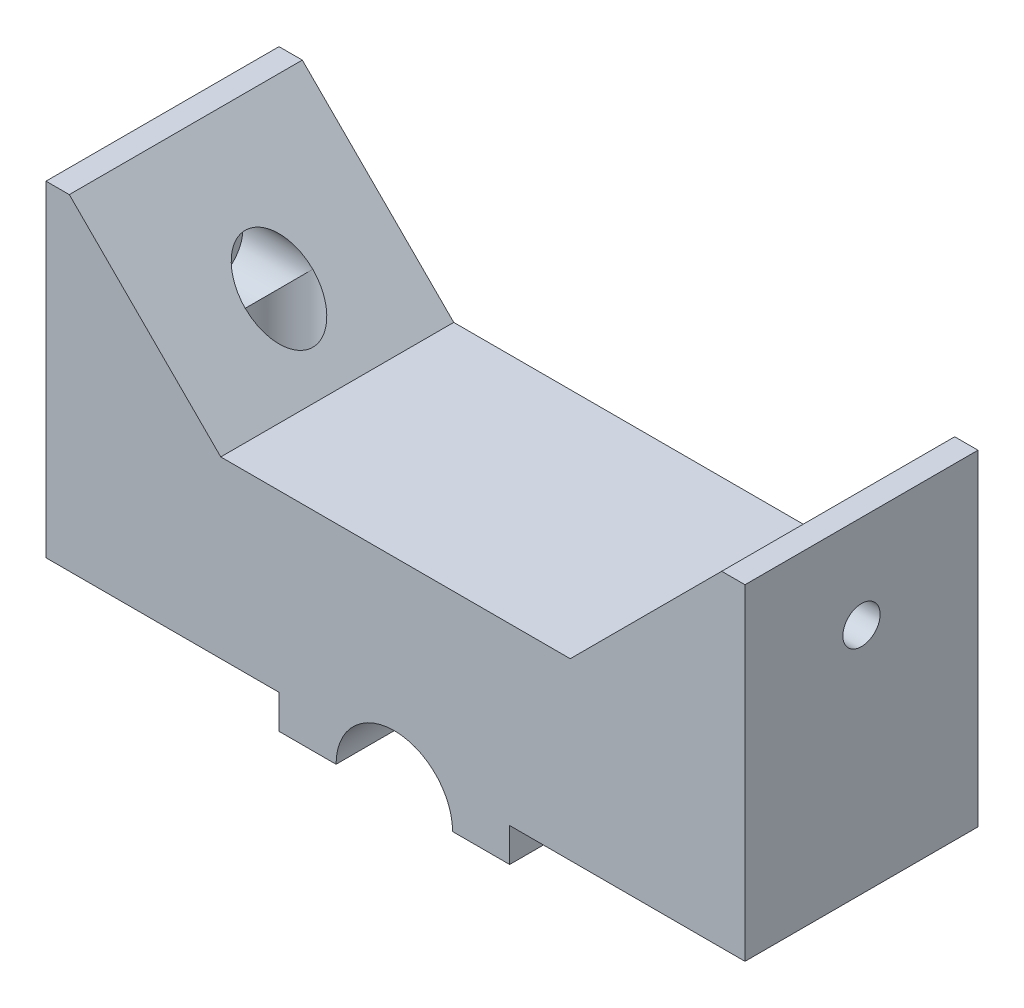
SolidWorks part; units mm, degrees
ref_plane "Plan de face" through (0, 0, 0) normal (0, 0, 1) x (1, 0, 0)
ref_plane "Plan de dessus" through (0, 0, 0) normal (0, 1, 0) x (1, 0, 0)
ref_plane "Plan de droite" through (0, 0, 0) normal (1, 0, 0) x (0, 0, -1)
sketch "Esquisse1" plane through (0, 0, 0) normal (0, 0, 1) x (1, 0, 0)
  line L0 (0, 30) -> (15, 15)
  line L1 (0, 0) -> (60, 0)
  line L2 (0, 0) -> (0, 15)
  line L3 (0, 15) -> (60, 15)
  line L4 (60, 0) -> (60, 15)
  line L5 (20, 0) -> (39.8, 0)
  line L6 (20, 0) -> (20, -2.9)
  line L7 (20, -2.9) -> (39.8, -2.9)
  line L8 (39.8, 0) -> (39.8, -2.9)
  line L9 (0, 15) -> (15, 15)
  line L10 (0, 15) -> (0, 30)
  line L11 (0, 30) -> (15, 30)
  line L12 (15, 15) -> (15, 30)
  line L13 (60, 15) -> (45, 15)
  line L14 (60, 15) -> (60, 30)
  line L15 (60, 30) -> (45, 30)
  line L16 (45, 15) -> (45, 30)
  line L17 (45, 15) -> (60, 30)
  line L19 (0, 30) -> (2, 30)
  line L20 (0, 30) -> (0, 28)
  line L21 (0, 28) -> (2, 28)
  line L22 (2, 30) -> (2, 28)
  line L23 (60, 30) -> (58, 30)
  line L24 (60, 30) -> (60, 28)
  line L25 (60, 28) -> (58, 28)
  line L26 (58, 30) -> (58, 28)
  dimension "D1" = 15
  dimension "D2" = 60
  dimension "D3" = 2.9
  dimension "D4" = 20
  dimension "D5" = 19.8
  dimension "D6" = 15
  dimension "D7" = 15
  dimension "D8" = 15
  dimension "D9" = 15
  dimension "D10" = 2
  dimension "D11" = 2
extrude "Boss.-Extru.1" add sketch "Esquisse1" along normal blind 5 contours L10 L3 L0 | L1 L4 L3 L2 | L17 L3 L14 | L8 L1 L6 L7 region at (5.0784, 19.8431, 0) region at (30, 7.5, 0) region at (54.9216, 19.8431, 0) region at (29.9, -1.45, 0)
sketch "Esquisse2" plane through (0, 0, 5) normal (0, 0, 1) x (1, 0, 0)
  line L10 (0, 28) -> (0, 0)
  line L11 (0, 0) -> (20, 0)
  line L12 (20, 0) -> (20, -2.9)
  line L13 (20, -2.9) -> (39.8, -2.9)
  line L14 (39.8, -2.9) -> (39.8, 0)
  line L15 (39.8, 0) -> (60, 0)
  line L16 (60, 0) -> (60, 28)
  line L17 (58, 28) -> (45, 15)
  line L18 (45, 15) -> (15, 15)
  line L19 (15, 15) -> (2, 28)
  line L20 (0, 28) -> (0, 0)
  line L21 (0, 0) -> (20, 0)
  line L22 (20, 0) -> (20, -2.9)
  line L23 (20, -2.9) -> (39.8, -2.9)
  line L24 (39.8, -2.9) -> (39.8, 0)
  line L25 (39.8, 0) -> (60, 0)
  line L26 (60, 0) -> (60, 28)
  line L27 (58, 28) -> (45, 15)
  line L28 (45, 15) -> (15, 15)
  line L29 (15, 15) -> (2, 28)
  line L32 (2, 28) -> (0, 28)
  line L33 (2, 28) -> (0, 28)
  line L34 (60, 28) -> (58, 28)
  line L35 (60, 28) -> (58, 28)
  circle A0 centre (29.9, -2.9) radius 5
  line M11 (0, 28) -> (0, 0)
  line M12 (0, 0) -> (20, 0)
  line M13 (20, 0) -> (20, -2.9)
  line M14 (20, -2.9) -> (39.8, -2.9)
  line M15 (39.8, -2.9) -> (39.8, 0)
  line M16 (39.8, 0) -> (60, 0)
  line M17 (60, 0) -> (60, 28)
  line M18 (58, 28) -> (45, 15)
  line M19 (45, 15) -> (15, 15)
  line M20 (15, 15) -> (2, 28)
  dimension "D2" = 10
  dimension "D1" = 0
extrude "Boss.-Extru.2" add sketch "Esquisse2" along normal blind 15 contours A0 M14 M15 M16 M17 M18 M19 M20 M11 M12 M13 region at (29.9984, 9.7289, 5)
sketch "Esquisse3" plane through (60, 0, 0) normal (1, 0, 0) x (0, 0, -1)
  line L0 (-20, 0) -> (-20, 28) construction
  line L5 (-20, 28) -> (0, 28) construction
  circle A0 centre (-10, 20) radius 1.6
  dimension "D3" = 3.2
  dimension "D1" = 10
  dimension "D2" = 8
extrude "Enlèv. mat.-Extru.1" cut sketch "Esquisse3" against normal through all contours A0 | A0 region at (60, 20, 10)
ref_plane "Plan1" through (30, 0, 0) normal (-1, 0, 0) x (0, 0, 1)
sketch "Esquisse4" plane through (30, 0, 0) normal (-1, 0, 0) x (0, 0, 1)
  circle A0 centre (10, 20) radius 1.6 construction
  circle A1 centre (10, 20) radius 1.6
  circle A2 centre (10, 20) radius 2.9
  dimension "D1" = 5.8
extrude "Enlèv. mat.-Extru.2" cut sketch "Esquisse4" against normal blind 26 and the other way blind 26
sketch "Esquisse5" plane through (0, 0, 0) normal (0, -1, 0) x (1, 0, 0)
  line L0 (39.8, 0) -> (60, 0) construction
  line L1 (60, 0) -> (60, 20) construction
  line L2 (60, 20) -> (39.8, 20) construction
  line L3 (39.8, 20) -> (39.8, 0) construction
  line L4 (0, 0) -> (20, 0) construction
  line L5 (20, 0) -> (20, 20) construction
  line L6 (20, 20) -> (0, 20) construction
  line L7 (0, 20) -> (0, 0) construction
  line L8 (39.8, 0) -> (60, 0)
  line L9 (60, 0) -> (60, 20)
  line L10 (60, 20) -> (39.8, 20)
  line L11 (39.8, 20) -> (39.8, 0)
  line L12 (0, 0) -> (20, 0)
  line L13 (20, 0) -> (20, 20)
  line L14 (20, 20) -> (0, 20)
  line L15 (0, 20) -> (0, 0)
  line L16 (0, 20) -> (20, 0)
  line L18 (39.8, 0) -> (60, 20)
  circle A0 centre (10, 10) radius 1.6
  circle A1 centre (49.9, 10) radius 1.6
  dimension "D1" = 3.2
  dimension "D2" = 3.2
extrude "Enlèv. mat.-Extru.3" cut sketch "Esquisse5" against normal blind 25 contours L16 A0 | L16 A0 | L18 A1 | L18 A1 region at (49.4222, 0, 10.4826) region at (50.3778, 0, 9.5174) region at (9.5198, 0, 9.5198) region at (10.4802, 0, 10.4802)
sketch "Esquisse6" plane through (0, 15, 0) normal (0, 1, 0) x (1, 0, 0)
  circle A0 centre (49.9, -10) radius 1.6 construction
  circle A1 centre (10, -10) radius 1.6 construction
  circle A2 centre (49.9, -10) radius 1.6
  circle A3 centre (10, -10) radius 1.6
  circle A4 centre (10, -10) radius 2.9
  circle A5 centre (49.9, -10) radius 2.9
  dimension "D1" = 5.8
  dimension "D2" = 5.8
extrude "Enlèv. mat.-Extru.4" cut sketch "Esquisse6" against normal blind 10 and the other way blind 25
